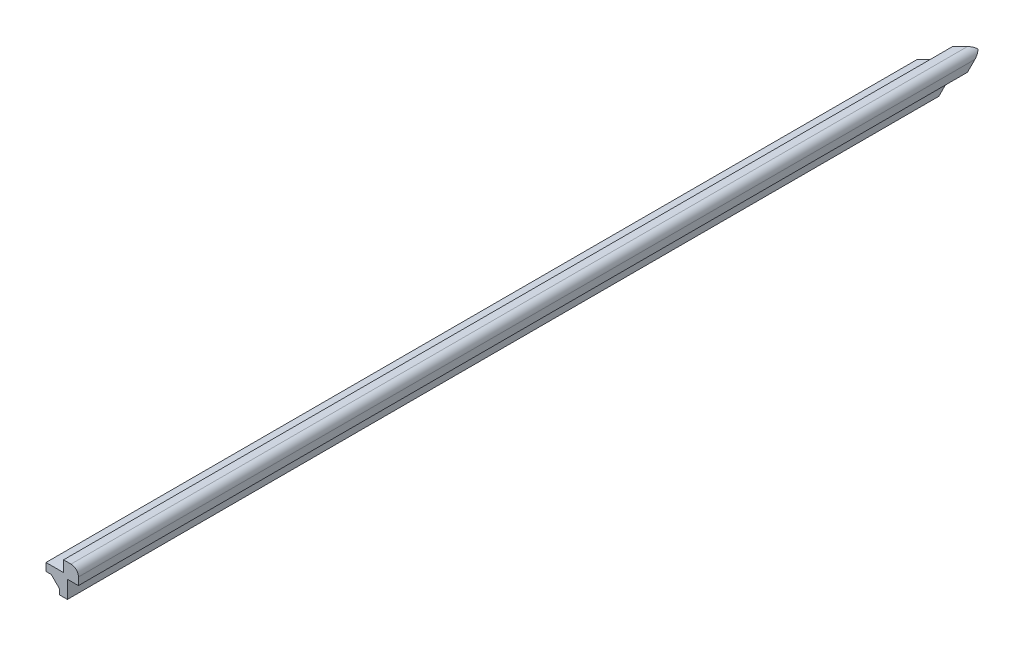
SolidWorks part; units mm, degrees
ref_plane "Front Plane" through (0, 0, 0) normal (0, 0, 1) x (1, 0, 0)
ref_plane "Top Plane" through (0, 0, 0) normal (0, 1, 0) x (1, 0, 0)
ref_plane "Right Plane" through (0, 0, 0) normal (1, 0, 0) x (0, 0, -1)
ref_axis "Axis1" through (0, 0, -88.99) along (0, 0, 1)
sketch "Sketch16" plane through (0, 0, 0) normal (0, 1, 0) x (1, 0, 0)
  line L0 (0, -127) -> (0, 127) construction
  point P2 (0, 0)
  dimension "D1" = 254
sketch "Sketch2" plane through (0, 0, 0) normal (0, 0, 1) x (1, 0, 0)
  line L0 (-7.3025, -1.5) -> (-2.54, -1.5) construction
  line L1 (-7.3025, -1.5) -> (-7.3025, 1.5) construction
  line L2 (-2.54, -1.5) -> (-2.54, 1.5) construction
  line L3 (-7.3025, 1.5) -> (-2.54, 1.5) construction
  line L4 (-2.54, 0) -> (0, 0) construction
  line L5 (0, 0) -> (0, -2.54) construction
  line L6 (-1.5, -2.54) -> (1.5, -2.54) construction
  line L7 (-1.5, -2.54) -> (-1.5, -7.3025) construction
  line L8 (1.5, -2.54) -> (1.5, -7.3025) construction
  line L9 (-1.5, -7.3025) -> (1.5, -7.3025) construction
  point P7 (0, -2.54)
  point P16 (1.5, 1.5)
  dimension "D1" = 3
  dimension "D2" = 4.7625
  dimension "D3" = 2.54
  dimension "D4" = 90
ref_plane "Plane1" through (0, 0, 0) normal (-1, 0, 0) x (0, -1, 0)
sketch "Sketch7" plane through (0, 0, 0) normal (0, 0, 1) x (1, 0, 0)
  line L0 (-7.3025, -1.5) -> (-2.54, -1.5)
  line L1 (-7.3025, -1.5) -> (-7.3025, -3.6212)
  line L2 (-2.54, -1.5) -> (-2.54, -3.6212)
  line L3 (-7.3025, -3.6212) -> (-2.54, -3.6212)
  dimension "D1" = 2.1212
extrude "Boss-Extrude2" add sketch "Sketch7" along normal mid plane 260.35 separate body
sketch "Sketch8" plane through (0, 0, 0) normal (0, 0, 1) x (1, 0, 0)
  line L0 (-1.5, -2.54) -> (-1.5, -7.3025)
  line L1 (-1.5, -2.54) -> (-3.6212, -2.54)
  line L2 (-1.5, -7.3025) -> (-3.6212, -7.3025)
  line L3 (-3.6212, -2.54) -> (-3.6212, -7.3025)
  line L4 (-2.54, -3.6212) -> (-2.54, -1.5) construction
extrude "Boss-Extrude3" add sketch "Sketch8" along normal mid plane 260.35
sketch "Sketch11" plane through (0, 0, 0) normal (0, 0, 1) x (1, 0, 0)
  line L0 (-2.54, 1.5) -> (-2.54, -1.5)
  line L1 (-2.54, -1.5) -> (-7.3025, -1.5)
  line L2 (-7.3025, -1.5) -> (-7.3025, -3.6212)
  line L3 (-7.3025, -3.6212) -> (-5.8663, -3.6212)
  line L4 (-7.3025, -3.6212) -> (-3.6212, -3.6212) construction
  line L5 (-5.8663, -3.6212) -> (-3.6212, -5.8663)
  line L6 (-3.6212, -3.6212) -> (-3.6212, -7.3025) construction
  line L7 (-3.6212, -5.8663) -> (-3.6212, -7.3025)
  line L8 (-3.6212, -7.3025) -> (-1.5, -7.3025)
  line L9 (-1.5, -7.3025) -> (-1.5, -2.54)
  line L10 (-1.5, -2.54) -> (1.5, -2.54)
  line L13 (-2.54, 1.5) -> (-2.54, -2.54) construction
  line L14 (-2.54, -2.54) -> (1.5, -2.54) construction
  line L15 (-2.54, 1.5) -> (-0.52, 1.5)
  line L17 (1.5, -0.52) -> (1.5, -2.54)
  circle A0 centre (-0.52, -0.52) radius 2.02 construction
  arc A1 (-0.52, 1.5) -> (1.5, -0.52) centre (-0.52, -0.52) cw
  dimension "D1" = 3.175
extrude "Boss-Extrude4" add sketch "Sketch11" along normal mid plane 260.35
sketch "Sketch14" plane through (0, 0, 0) normal (0, 1, 0) x (1, 0, 0)
  line L0 (-7.3025, -104.0263) -> (-7.3025, -149.9737)
  line L1 (-7.3025, -130.175) -> (-7.3025, 130.175) construction
  line L2 (-7.3025, -149.9737) -> (7.3025, -149.9737)
  line L4 (7.3025, -149.9737) -> (-7.3025, -104.0263)
  line L5 (0, 88.99) -> (0, -88.99) construction
  line L6 (0, -127) -> (0, 127) construction
  line L8 (-7.3025, 104.0263) -> (7.3025, 149.9737)
  line L9 (7.3025, 149.9737) -> (-7.3025, 149.9737)
  line L10 (-7.3025, 149.9737) -> (-7.3025, 104.0263)
  point P5 (0, -127)
  point P13 (0, 127)
  dimension "D2" = 17.634
  dimension "D1" = 17.634
extrude "Cut-Extrude4" [suppressed] cut sketch "Sketch14" against normal through all both and the other way through all
sketch "Sketch17" plane through (0, 0, 0) normal (-1, 0, 0) x (0, -1, 0)
  line L0 (7.3025, 144.6298) -> (7.3025, 109.3702)
  line L2 (7.3025, 109.3702) -> (-7.3025, 144.6298)
  line L3 (-7.3025, 144.6298) -> (7.3025, 144.6298)
  line L4 (7.3025, -109.3702) -> (-7.3025, -144.6298)
  line L5 (-7.3025, -144.6298) -> (7.3025, -144.6298)
  line L6 (7.3025, -144.6298) -> (7.3025, -109.3702)
  point P4 (0, 127)
  point P10 (0, -127)
  dimension "D1" = 22.5
  dimension "D2" = 22.5
  dimension "D3" = 7.3025
extrude "Cut-Extrude5" [suppressed] cut sketch "Sketch17" against normal through all both and the other way through all
ref_plane "Midplane" through (0, 0, 0) normal (-0.7071, 0.7071, 0) x (0.7071, 0.7071, 0)
sketch "Sketch18" plane through (0, 0, -113.7049) normal (-0.5774, -0.5774, 0.5774) x (-0.7071, 0, -0.7071)
  line L0 (0, 0) -> (0, -73.3235)
  line L1 (0, -73.3235) -> (-63.5, 36.6617) construction
  line L2 (-63.5, 36.6617) -> (0, 0)
  line L3 (63.5, 36.6617) -> (-63.5, 36.6617)
  line L4 (0, -73.3235) -> (63.5, 36.6617)
  line L5 (63.5, 36.6617) -> (0, 0) construction
  point P4 (-208.9101, 136.7438)
  point P5 (-205.7971, 128.2942)
  point P6 (0, 0)
  point P9 (0, 0)
  dimension "D1" = 127
extrude "Cut-Extrude6" cut sketch "Sketch18" against normal through all both and the other way through all
equation "\"plate_thickness\"= 3mm"
equation "\"D1@Sketch2\"=\"plate_thickness\""
equation "\"joiner_lip_width\"= .1875"
equation "\"D2@Sketch2\"=\"joiner_lip_width\""
equation "\"face_gap\"=0.1"
equation "\"D3@Sketch2\"=\"face_gap\""
equation "\"inside_angle\"= 90"
equation "\"joiner_thickness\"= 0.0835128"
equation "\"edge_length\"= 10"
equation "\"Face1_TopLip\"= \"angle\" * 2"
equation "\"Face1_BottomLip\"= \"angle\" * 2"
equation "\"Face2_TopLip\"= 45deg"
equation "\"Face2_BottomLip\"= 45deg"
equation "\"D1@Sketch7\"=\"joiner_thickness\""
equation "\"D1@Boss-Extrude2\"=\"Extrude_to\""
equation "\"D1@Boss-Extrude3\"=\"Extrude_to\""
equation "\"D1@Boss-Extrude4\"=\"Extrude_to\""
equation "\"D4@Sketch2\"=\"inside_angle\""
equation "\"Extrude_to\"= \"edge_length\" + .25"
equation "\"D2@Sketch14\"=\"Face1_BottomLip\"/2"
equation "\"D1@Sketch16\"=\"edge_length\""
equation "\"D1@Sketch14\"=\"Face1_TopLip\"/2"
equation "\"D1@Sketch17\"=\"Face2_TopLip\"/2"
equation "\"D2@Sketch17\"=\"Face2_BottomLip\"/2"
equation "\"D3@Sketch17\"=\"joiner_lip_width\"+\"face_gap\""
equation "\"angle\"= atn ( 0.1 / ( ( 3.7085 - 3.0793 ) / 2 ) )"
equation "\"D2@Sketch5\"=\"Face2_TopLip\"/2"
equation "\"D1@Sketch5\"=\"Face2_BottomLip\"/2"
equation "\"D2@Sketch4\"=\"Face1_TopLip\"/2"
equation "\"D1@Sketch4\"=\"Face1_BottomLip\"/2"
equation "\"D1\" = \"edge_length\""
equation "\"D2@Sketch12\"=\"Face1_TopLip\"/2"
equation "\"D1@Sketch12\"=\"Face1_BottomLip\"/2"
